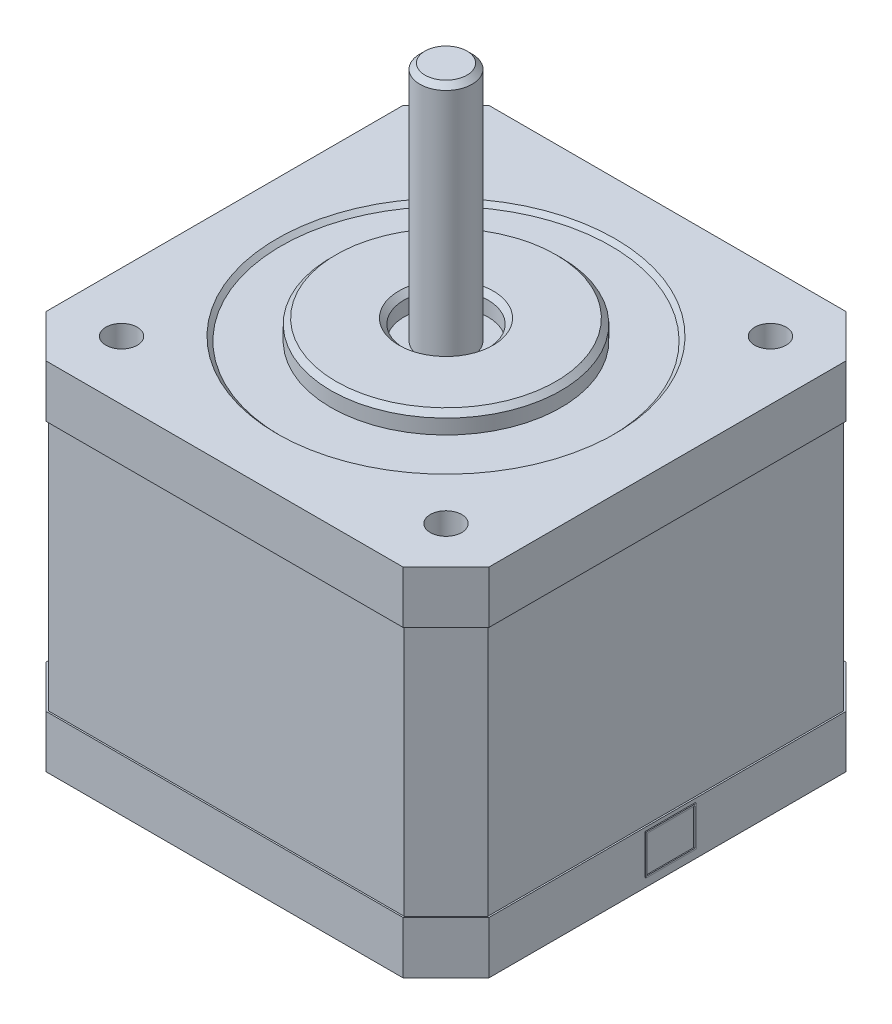
SolidWorks part; units mm, degrees
ref_plane "Front Plane" through (0, 0, 0) normal (0, 0, 1) x (1, 0, 0)
ref_plane "Top Plane" through (0, 0, 0) normal (0, 1, 0) x (1, 0, 0)
ref_plane "Right Plane" through (0, 0, 0) normal (1, 0, 0) x (0, 0, -1)
sketch "Sketch1" plane through (0, 0, 0) normal (0, 1, 0) x (1, 0, 0)
  line L1 (-21, 21) -> (21, 21)
  line L2 (-21, 21) -> (-21, -21)
  line L3 (-21, -21) -> (21, -21)
  line L4 (21, 21) -> (21, -21)
  line L5 (-21, 21) -> (21, -21) construction
  line L6 (-21, -21) -> (21, 21) construction
  point P0 (0, 0)
  dimension "D1" = 42
  dimension "D2" = 42
extrude "Boss-Extrude1" add sketch "Sketch1" along normal blind 34
chamfer "Chamfer1" distance 4 angle 45 4 edges at (-21, 17, -21) (21, 17, -21) (21, 17, 21) (-21, 17, 21)
sketch "Sketch6" plane through (0, 34, 0) normal (0, 1, 0) x (1, 0, 0)
  line L16 (17.0621, 21.15) -> (-17.0621, 21.15)
  line L17 (-17.0621, 21.15) -> (-21.15, 17.0621)
  line L18 (-21.15, 17.0621) -> (-21.15, -17.0621)
  line L19 (-21.15, -17.0621) -> (-17.0621, -21.15)
  line L20 (-17.0621, -21.15) -> (17.0621, -21.15)
  line L21 (17.0621, -21.15) -> (21.15, -17.0621)
  line L22 (21.15, -17.0621) -> (21.15, 17.0621)
  line L23 (21.15, 17.0621) -> (17.0621, 21.15)
  line L24 (17.0621, 21.15) -> (-17.0621, 21.15)
  line L25 (-17.0621, 21.15) -> (-21.15, 17.0621)
  line L26 (-21.15, 17.0621) -> (-21.15, -17.0621)
  line L27 (-21.15, -17.0621) -> (-17.0621, -21.15)
  line L28 (-17.0621, -21.15) -> (17.0621, -21.15)
  line L29 (17.0621, -21.15) -> (21.15, -17.0621)
  line L30 (21.15, -17.0621) -> (21.15, 17.0621)
  line L31 (21.15, 17.0621) -> (17.0621, 21.15)
  dimension "D1" = 0.15
extrude "Boss-Extrude4" add sketch "Sketch6" against normal blind 5
sketch "Sketch7" plane through (0, 0, 0) normal (0, -1, 0) x (1, 0, 0)
  line L16 (-21.15, 17.0621) -> (-21.15, -17.0621)
  line L17 (-21.15, -17.0621) -> (-17.0621, -21.15)
  line L18 (-17.0621, -21.15) -> (17.0621, -21.15)
  line L19 (17.0621, -21.15) -> (21.15, -17.0621)
  line L20 (21.15, -17.0621) -> (21.15, 17.0621)
  line L21 (21.15, 17.0621) -> (17.0621, 21.15)
  line L22 (17.0621, 21.15) -> (-17.0621, 21.15)
  line L23 (-17.0621, 21.15) -> (-21.15, 17.0621)
  line L24 (-21.15, 17.0621) -> (-21.15, -17.0621)
  line L25 (-21.15, -17.0621) -> (-17.0621, -21.15)
  line L26 (-17.0621, -21.15) -> (17.0621, -21.15)
  line L27 (17.0621, -21.15) -> (21.15, -17.0621)
  line L28 (21.15, -17.0621) -> (21.15, 17.0621)
  line L29 (21.15, 17.0621) -> (17.0621, 21.15)
  line L30 (17.0621, 21.15) -> (-17.0621, 21.15)
  line L31 (-17.0621, 21.15) -> (-21.15, 17.0621)
  dimension "D1" = 0.15
extrude "Boss-Extrude5" add sketch "Sketch7" against normal blind 5
sketch "Sketch2" plane through (0, 34, 0) normal (0, 1, 0) x (1, 0, 0)
  circle A0 centre (0, 0) radius 16.25
  dimension "D1" = 32.5
extrude "Cut-Extrude1" cut sketch "Sketch2" against normal blind 0.4
sketch "Sketch3" plane through (0, 33.6, 0) normal (0, 1, 0) x (1, 0, 0)
  circle A0 centre (0, 0) radius 4
  circle A1 centre (0, 0) radius 11
  dimension "D1" = 8
  dimension "D2" = 22
extrude "Boss-Extrude2" add sketch "Sketch3" along normal blind 1.9
sketch "Sketch4" plane through (0, 33.6, 0) normal (0, 1, 0) x (1, 0, 0)
  circle A0 centre (0, 0) radius 2.5
  dimension "D1" = 5
extrude "Boss-Extrude3" add sketch "Sketch4" along normal blind 23
chamfer "Chamfer2" distance 0.5 angle 45 4 edges at (0, 35.5, 4) (0, 35.5, 11) (0, 56.6, 2.5) (0, 33.6, 16.25)
sketch "Sketch5" plane through (0, 34, 0) normal (0, 1, 0) x (1, 0, 0)
  circle A0 centre (-15.5, 15.5) radius 1.5
  circle A1 centre (15.5, 15.5) radius 1.5
  circle A2 centre (15.5, -15.5) radius 1.5
  circle A3 centre (-15.5, -15.5) radius 1.5
  point P12 (0, 0)
  dimension "D1" = 15.5
  dimension "D2" = 15.5
  dimension "D3" = 3
  dimension "D4" = 4
extrude "Cut-Extrude2" cut sketch "Sketch5" against normal blind 5
sketch "Sketch8" plane through (21.15, 0, 0) normal (1, 0, 0) x (0, 0, -1)
  line L0 (17.0621, 0) -> (-17.0621, 0) construction
  line L1 (-1.9802, 4.5) -> (2.5198, 4.5)
  line L2 (-1.9802, 4.5) -> (-1.9802, 1)
  line L3 (-1.9802, 1) -> (2.5198, 1)
  line L4 (2.5198, 4.5) -> (2.5198, 1)
  line L5 (-1.9802, 4.5) -> (2.5198, 1) construction
  line L6 (-1.9802, 1) -> (2.5198, 4.5) construction
  line L7 (-2.1302, 4.65) -> (2.6698, 4.65)
  line L8 (2.6698, 4.65) -> (2.6698, 0.85)
  line L9 (-2.1302, 0.85) -> (2.6698, 0.85)
  line L10 (-2.1302, 4.65) -> (-2.1302, 0.85)
  point P0 (0.2698, 2.75)
  dimension "D1" = 1
  dimension "D2" = 3.5
  dimension "D3" = 4.5
  dimension "D4" = 0.15
extrude "Boss-Extrude6" add sketch "Sketch8" along normal blind 0.1
